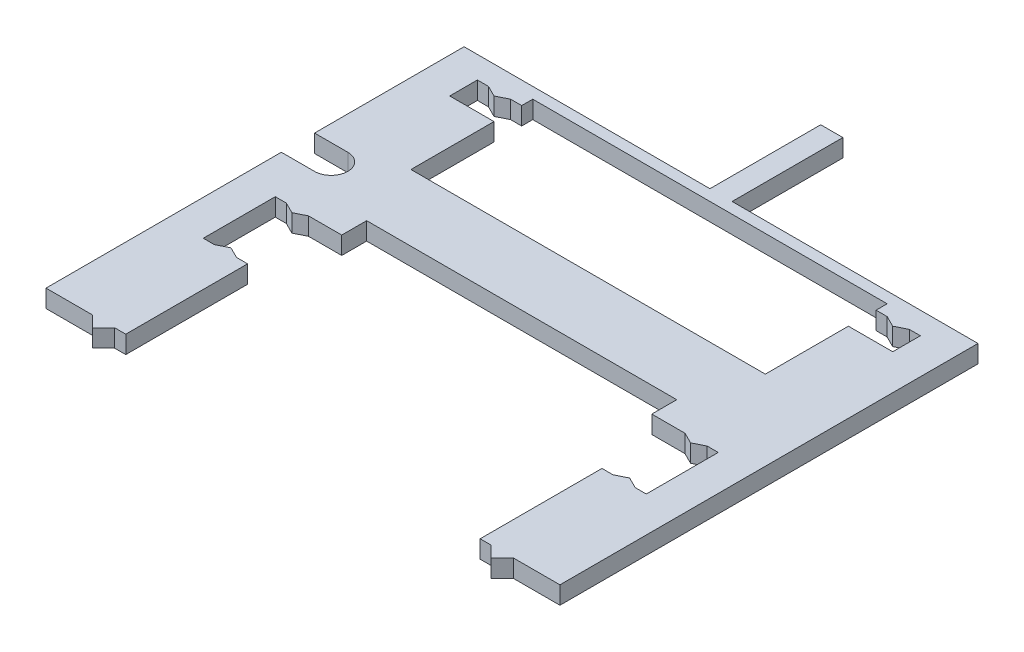
SolidWorks part; units mm, degrees
ref_plane "Front Plane" through (0, 0, 0) normal (0, 0, 1) x (1, 0, 0)
ref_plane "Top Plane" through (0, 0, 0) normal (0, 1, 0) x (1, 0, 0)
ref_plane "Right Plane" through (0, 0, 0) normal (1, 0, 0) x (0, 0, -1)
sketch "Sketch1" plane through (0, 0, 0) normal (0, 1, 0) x (1, 0, 0)
  line L0 (-65.8326, 0) -> (-61.6296, 0)
  line L1 (-58.6296, 0) -> (-58.6296, 11)
  line L2 (-58.6296, 11) -> (-59.6296, 11)
  line L3 (-62.6296, 11) -> (-62.6296, 17.5)
  line L4 (-62.6296, 17.5) -> (-61.6296, 17.5)
  line L5 (-61.6296, 17.5) -> (-60.6296, 17)
  line L6 (-60.6296, 38.9626) -> (-60.6296, -4.5955) construction
  line L7 (-56.6296, 17.5) -> (-56.6296, 19.75)
  line L8 (-26.6296, 25.75) -> (-58.6296, 25.75)
  line L9 (-58.6296, 25.75) -> (-58.6296, 33.25)
  line L10 (-58.6296, 35.75) -> (-58.6296, 36.75)
  line L11 (-42.6296, 47.75) -> (-42.6296, 3.1352) construction
  line L12 (-65.8326, 0) -> (-65.8326, 21.25)
  line L13 (-65.8326, 37.75) -> (-43.6296, 37.75)
  line L14 (-24.6296, 38.9626) -> (-24.6296, -4.5955) construction
  line L15 (-25.6296, 35.75) -> (-26.6296, 35.75)
  line L16 (-24.6296, 35.25) -> (-25.6296, 35.75)
  line L17 (-23.6296, 35.75) -> (-24.6296, 35.25)
  line L18 (-22.6296, 35.75) -> (-23.6296, 35.75)
  line L19 (-58.6296, 33.25) -> (-62.6296, 33.25)
  line L20 (-22.6296, 33.25) -> (-22.6296, 35.75)
  line L21 (-25.6296, 17.5) -> (-28.6296, 17.5)
  line L22 (-24.6296, 17) -> (-25.6296, 17.5)
  line L23 (-25.6296, 0) -> (-26.6296, 0)
  line L24 (-24.6296, -1) -> (-25.6296, 0)
  line L25 (-23.6296, 0) -> (-24.6296, -1)
  line L26 (-24.6296, 11.5) -> (-25.6296, 11)
  line L27 (-62.6296, 11) -> (-61.6296, 11)
  line L28 (-61.6296, 11) -> (-60.6296, 11.5)
  line L29 (-60.6296, 11.5) -> (-59.6296, 11)
  line L30 (-61.6296, 0) -> (-60.6296, -1)
  line L31 (-60.6296, -1) -> (-59.6296, 0)
  line L32 (-59.6296, 0) -> (-58.6296, 0)
  line L33 (-60.6296, 17) -> (-59.6296, 17.5)
  line L34 (-59.6296, 17.5) -> (-56.6296, 17.5)
  line L35 (-56.6296, 19.75) -> (-28.6296, 19.75)
  line L36 (-62.6296, 33.25) -> (-62.6296, 35.75)
  line L37 (-62.6296, 35.75) -> (-61.6296, 35.75)
  line L38 (-58.6296, 36.75) -> (-26.6296, 36.75)
  line L39 (-61.6296, 35.75) -> (-60.6296, 35.25)
  line L40 (-60.6296, 35.25) -> (-59.6296, 35.75)
  line L41 (-59.6296, 35.75) -> (-58.6296, 35.75)
  line L42 (-23.6296, 11) -> (-24.6296, 11.5)
  line L43 (-22.6296, 11) -> (-23.6296, 11)
  line L44 (-26.6296, 33.25) -> (-22.6296, 33.25)
  line L45 (-19.4266, 0) -> (-19.4266, 37.75)
  line L46 (-26.6296, 35.75) -> (-26.6296, 36.75)
  line L47 (-26.6296, 25.75) -> (-26.6296, 33.25)
  line L48 (-28.6296, 17.5) -> (-28.6296, 19.75)
  line L49 (-23.6296, 17.5) -> (-24.6296, 17)
  line L50 (-22.6296, 17.5) -> (-23.6296, 17.5)
  line L51 (-22.6296, 11) -> (-22.6296, 17.5)
  line L52 (-26.6296, 11) -> (-25.6296, 11)
  line L53 (-26.6296, 0) -> (-26.6296, 11)
  line L54 (-19.4266, 0) -> (-23.6296, 0)
  line L55 (-43.6296, 37.75) -> (-43.6296, 47.75)
  line L56 (-43.6296, 47.75) -> (-41.6296, 47.75)
  line L57 (-41.6296, 47.75) -> (-41.6296, 37.75)
  line L58 (-41.6296, 37.75) -> (-19.4266, 37.75)
  line L59 (-62.8326, 24.25) -> (-65.8326, 24.25)
  line L60 (-62.8326, 21.25) -> (-65.8326, 21.25)
  line L61 (-65.8326, 24.25) -> (-65.8326, 37.75)
  arc A0 (-62.8326, 21.25) -> (-62.8326, 24.25) centre (-62.8326, 22.75) ccw
  point P19 (-42.6296, 34.75)
  point P20 (-42.6296, 37.75)
  point P26 (-42.6296, 36.75)
  point P29 (-42.6296, 19.75)
  point P62 (-42.6296, 25.75)
  dimension "D26" = 3
  dimension "D27" = 3
  dimension "D1" = 23.203
  dimension "D2" = 16
  dimension "D3" = 1
  dimension "D4" = 1
  dimension "D5" = 1
  dimension "D6" = 2
  dimension "D7" = 0.5
  dimension "D8" = 6.5
  dimension "D9" = 1
  dimension "D10" = 1
  dimension "D11" = 1
  dimension "D12" = 11
  dimension "D13" = 0.5
  dimension "D14" = 1
  dimension "D15" = 1
  dimension "D16" = 2.25
  dimension "D17" = 3
  dimension "D18" = 6
  dimension "D19" = 1
  dimension "D20" = 7.5
  dimension "D21" = 16
  dimension "D22" = 20
  dimension "D23" = 1
  dimension "D24" = 1
  dimension "D25" = 0.5
  dimension "D28" = 2.5
  dimension "D29" = 2
  dimension "D30" = 10
extrude "Boss-Extrude1" add sketch "Sketch1" along normal blind 1.6
